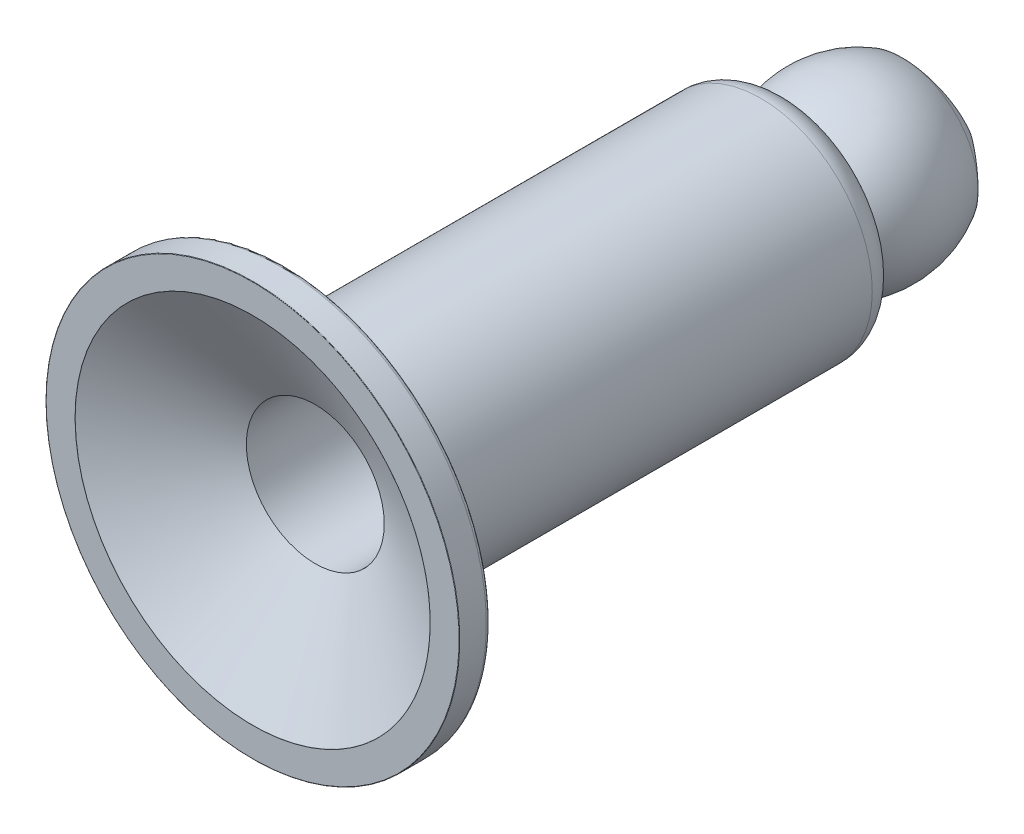
SolidWorks part; units mm, degrees
ref_plane "Front" through (0, 0, 0) normal (0, 0, 1) x (1, 0, 0)
ref_plane "Top" through (0, 0, 0) normal (0, 1, 0) x (1, 0, 0)
ref_plane "Right" through (0, 0, 0) normal (1, 0, 0) x (0, 0, -1)
sketch "Sketch1" plane through (0, 0, 0) normal (1, 0, 0) x (0, 0, -1)
  line L0 (-27.2034, 0) -> (-1.8034, 0) construction
  line L1 (-1.8034, 0) -> (0, 0) construction
  line L2 (0, 0) -> (9.6266, 0) construction
  line L3 (9.6266, 0) -> (12.4841, 0) construction
  line L4 (-1.1768, 4.4196) -> (0, 2.3813) construction
  line L5 (0, -2.3813) -> (-1.1768, -4.4196) construction
  line L8 (0, 4.4196) -> (0, -4.4196) construction
  line L9 (9.6266, 2.3813) -> (9.6266, -2.3813) construction
  point P7 (-1.8034, 4.4196)
  point P10 (-1.8034, -4.4196)
  point P25 (-1.8034, 1.4478)
  dimension "Head Height" = 1.8034
  dimension "D5" = 2.8575
  dimension "Diameter" = 4.7625
  dimension "Head Diameter" = 8.8392
  dimension "Countersink Angle" = 120
  dimension "Mandrel OD" = 2.8956
  dimension "Length" = 11.43
sketch "Sketch2" plane through (0, 0, 0) normal (1, 0, 0) x (0, 0, -1)
  line L0 (-27.2034, 0) -> (-27.2034, 1.4478)
  line L1 (-1.8034, 4.4196) -> (-1.8034, 3.793)
  line L2 (-1.8034, 4.4196) -> (-1.1768, 4.4196)
  line L3 (0, 0) -> (0, 4.4196) construction
  line L4 (-1.8034, 0) -> (-1.8034, 0.7239) construction
  line L5 (9.0551, 2.3812) -> (0, 2.3812)
  line L6 (9.6266, 2.3813) -> (9.6266, -2.3813) construction
  line L7 (-1.1768, 4.4196) -> (0, 2.3813) construction
  line L8 (0, 0) -> (9.6266, 0) construction
  line L9 (9.6266, 1.905) -> (12.4841, 1.905) construction
  line L10 (9.6266, 1.6669) -> (9.4075, 1.4478)
  line L11 (9.4075, 1.4478) -> (9.6266, 1.4478)
  line L12 (-27.2034, 0) -> (9.6266, 0)
  line L13 (-1.8034, 1.4478) -> (-1.8034, 0) construction
  line L14 (9.6266, 1.4478) -> (9.6266, 1.905) construction
  line L15 (12.4841, 0) -> (12.4841, 1.905) construction
  line L16 (12.076, 1.6193) -> (12.4841, 1.905) construction
  line L17 (-0.464, 1.4732) -> (4.5275, 1.4732)
  line L18 (12.076, 1.6193) -> (12.076, 0)
  line L19 (-1.1768, 4.4196) -> (0, 2.3812)
  line L20 (-1.8034, 1.4478) -> (-27.2034, 1.4478)
  line L21 (4.5275, 1.4732) -> (4.5275, 1.4478)
  line L22 (4.5275, 1.4478) -> (-1.8034, 1.4478)
  line L23 (12.076, 0) -> (9.6266, 0)
  line L24 (-1.8034, 3.793) -> (-0.464, 1.4732)
  arc A0 (9.0551, 2.3812) -> (9.6266, 1.6669) centre (9.0551, 1.7955) cw
  arc A1 (9.6266, 1.4478) -> (12.076, 1.6193) centre (10.9819, -0.3324) cw
  arc A2 (12.076, 1.6193) -> (12.4841, 0) centre (9.0676, 0) cw construction
  point P39 (4.5275, 2.3812)
  dimension "D1" = 0.5715
  dimension "D2" = 45
  dimension "D3" = 3.3337
  dimension "D4" = 3.81
  dimension "D5" = 35
  dimension "D6" = 3.2385
  dimension "D7" = 0.0254
revolve "Revolve1" add sketch "Sketch2" angle 360 about L12
sketch "Sketch3" plane through (0, 0, 0) normal (0, 1, 0) x (1, 0, 0)
  line L0 (0, -27.2034) -> (1.651, -25.0518)
  line L1 (-1.4478, -27.2034) -> (1.4478, -27.2034) construction
  line L3 (0, -27.2034) -> (0, -27.7114) construction
  line L4 (0, -27.2034) -> (-1.651, -25.0518)
  line L5 (-1.651, -25.0518) -> (-1.651, -27.7114)
  line L6 (-1.651, -27.7114) -> (1.651, -27.7114)
  line L7 (1.651, -27.7114) -> (1.651, -25.0518)
  dimension "D1" = 75
  dimension "D2" = 0.2032
  dimension "D3" = 0.508
extrude "Cut-Extrude1" cut sketch "Sketch3" against normal through all both and the other way through all
sketch "Sketch5" plane through (0, 0, 0) normal (1, 0, 0) x (0, 0, -1)
  line L0 (-27.2034, 0) -> (-25.3166, 1.7653)
  line L1 (-27.2034, -1.4478) -> (-27.2034, 1.4478) construction
  line L2 (-25.3166, 1.7653) -> (-27.5209, 1.7653)
  line L3 (-27.5209, 1.7653) -> (-27.5209, -1.7653)
  line L4 (-27.5209, -1.7653) -> (-25.3166, -1.7653)
  line L5 (-25.3166, -1.7653) -> (-27.2034, 0)
  line L6 (-27.2034, 0) -> (-9.2614, 0) construction
  line L7 (4.5276, 1.4478) -> (-27.2034, 1.4478) construction
  line L8 (-25.3166, 0) -> (-25.3166, 1.7653) construction
  ellipse E0 centre (-27.2034, 0) end of major axis (-29.0902, 0) minor radius 1.4478 (-27.2034, -1.4478) -> (-27.2034, 1.4478) ccw construction
  dimension "D1" = 0.3175
  dimension "D2" = 0.3175
extrude "Cut-Extrude2" cut sketch "Sketch5" against normal through all both and the other way through all
sketch "Sketch10" plane through (0, 0, 0) normal (1, 0, 0) x (0, 0, -1)
  line L6 (12.076, 1.6193) -> (12.4841, 0)
  line L7 (12.4841, 0) -> (12.076, -1.6193)
  line L8 (12.076, -1.6193) -> (12.076, 1.6193)
extrude "Boss-Extrude1" add sketch "Sketch10" along normal mid plane 3.81
sketch "Sketch12" plane through (0, 0, 0) normal (0, 1, 0) x (1, 0, 0)
  line L0 (1.905, 12.4841) -> (-1.905, 12.4841) construction
  line L1 (-0.9226, 12.4841) -> (-0.9226, 15.9811)
  line L2 (-0.9226, 15.9811) -> (-4.4196, 15.9811)
  line L3 (-4.4196, 15.9811) -> (-4.4196, 9.6266)
  line L4 (-4.4196, 9.6266) -> (-1.4478, 9.6266)
  line L10 (-4.4196, -1.1768) -> (-4.4196, -1.8034) construction
  arc A0 (-1.6192, 12.076) -> (-1.4478, 9.6266) centre (0.3324, 10.9819) ccw
  arc A1 (0.9652, 11.7348) -> (1.147, 13.3888) centre (-0.0003, 12.6779) ccw
  arc A3 (-1.6192, 12.076) -> (-1.4478, 9.6266) centre (0.3324, 10.9819) ccw
  arc A4 (-1.6192, 12.076) -> (-0.9226, 12.4841) centre (-0.9226, 11.6855) cw
revolve "Cut-Revolve1" cut sketch "Sketch12" angle 360 about L2
sketch "Sketch13" plane through (0, 0, 0) normal (0, 1, 0) x (1, 0, 0)
  line L0 (-0.9226, 12.4841) -> (-1.6192, 12.076)
  line L1 (-1.6192, 12.076) -> (-1.6192, 15.9811)
  line L2 (-1.6192, 15.9811) -> (-0.9226, 15.9811)
  line L3 (-0.9226, 15.9811) -> (-0.9226, 12.4841)
  line L4 (-0.9226, 15.9811) -> (-4.4196, 15.9811) construction
  line L5 (0, 0) -> (0, 15.9811) construction
  line L6 (1.6192, 12.076) -> (1.6192, 15.9811)
  line L7 (0.9226, 12.4841) -> (1.6192, 12.076)
  line L8 (0.9226, 15.9811) -> (0.9226, 12.4841)
  line L9 (1.6192, 15.9811) -> (0.9226, 15.9811)
extrude "Cut-Extrude6" cut sketch "Sketch13" against normal through all both and the other way through all
fillet "Fillet1" radius 0.0902 2 edges at (4.4196, 0, 1.1768) (2.3812, 0, 0)
fillet "Fillet2" radius 0.009 2 edges at (3.793, 0, 1.8034) (4.4196, 0, 1.8034)
ref_plane "Plane1" through (0, 0, 27.2034) normal (0, 0, 1) x (1, 0, 0)
sketch "Sketch14" plane through (0, 0, 27.2034) normal (0, 0, 1) x (1, 0, 0)
  circle A0 centre (0, 0) radius 1.4732
  circle A1 centre (0, 0) radius 1.4732 construction
extrude "Cut-Extrude7" cut sketch "Sketch14" against normal up to surface (31.7309 mm away) up to face at (1.4478, 0, -4.5276)
equation "\"D5@Sketch1\"=\"Diameter@Sketch1\"*0.6"
equation "\"D2@Sketch5\"=\"D1@Sketch5\""
equation "\"D1@Sketch2\"=\"Length@Sketch1\"*0.05"
equation "\"D3@Sketch2\"=\"Diameter@Sketch1\"*0.7"
equation "\"D4@Sketch2\"=\"Diameter@Sketch1\"*0.8"
equation "\"D6@Sketch2\"=\"D4@Sketch2\"*0.85"
equation "\"D1@Boss-Extrude1\"=\"D4@Sketch2\""
equation "\"D1@Fillet1\"=\"Head Height@Sketch1\"*0.05"
equation "\"D1@Fillet2\"=\"D1@Fillet1\"*0.1"
